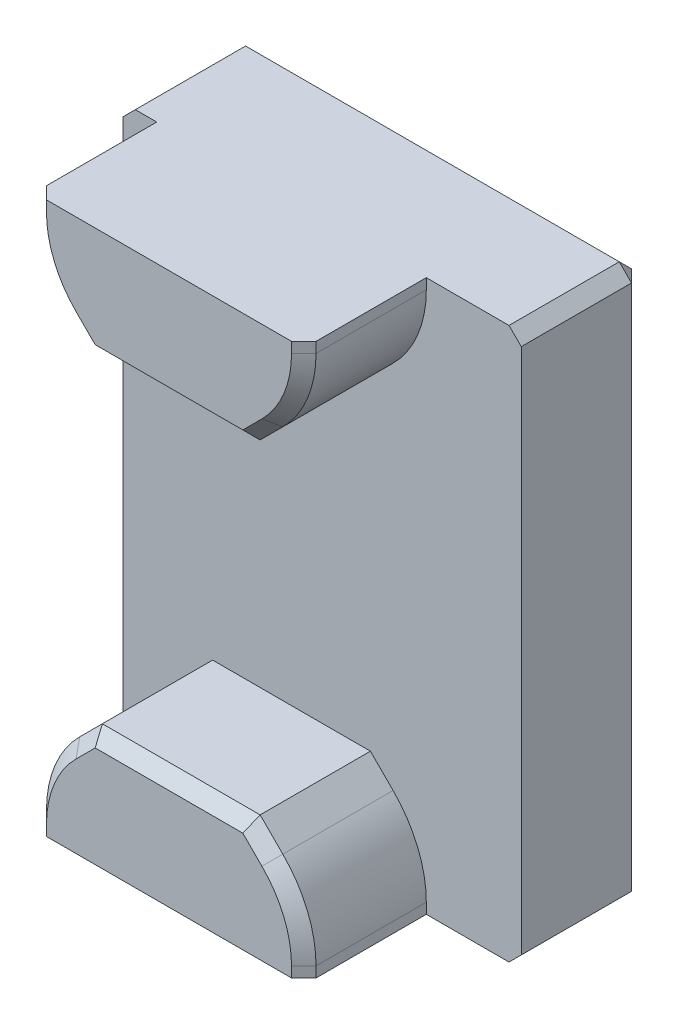
SolidWorks part; units mm, degrees
ref_plane "Front" through (0, 0, 0) normal (0, 0, 1) x (1, 0, 0)
ref_plane "Top" through (0, 0, 0) normal (0, 1, 0) x (1, 0, 0)
ref_plane "Right" through (0, 0, 0) normal (1, 0, 0) x (0, 0, -1)
sketch "Sketch1" plane through (0, 0, 0) normal (0, 0, 1) x (1, 0, 0)
  line L0 (2.75, -11.5) -> (2.75, -5) construction
  line L1 (-2.75, -4.5) -> (2.75, -4.5)
  line L2 (-2.75, -4.5) -> (-2.75, 4.5)
  line L3 (-2.75, 4.5) -> (2.75, 4.5)
  line L4 (2.75, -4.5) -> (2.75, 4.5) construction
  line L5 (-2.75, -4.5) -> (2.75, 4.5) construction
  line L6 (-2.75, 4.5) -> (2.75, -4.5) construction
  line L7 (2.35, -4.5) -> (3.75, -4.5) construction
  line L8 (2.75, 4.5) -> (3.75, 4.5)
  line L9 (3.75, 4.5) -> (3.75, -4.5)
  line L10 (3.75, -4.5) -> (2.75, -4.5)
  point P0 (0, 0)
extrude "Boss-Extrude1" add sketch "Sketch1" against normal blind 2
sketch "Sketch2" plane through (0, 0, 0) normal (0, 0, 1) x (1, 0, 0)
  line L9 (1.2879, -2.65) -> (-1.2879, -2.65)
  line L10 (-1.2879, -2.65) -> (-1.6581, -3.0203)
  line L11 (-2.2, -4.3284) -> (-2.2, -5.1716)
  line L12 (-1.6581, -6.4797) -> (-1.2879, -6.85)
  line L13 (-1.2879, -6.85) -> (1.2879, -6.85)
  line L14 (1.2879, -6.85) -> (1.6581, -6.4797)
  line L15 (2.2, -5.1716) -> (2.2, -4.3284)
  line L16 (1.6581, -3.0203) -> (1.2879, -2.65)
  line L41 (1.35, -7) -> (1.7642, -6.5858)
  line L46 (-1.35, -7) -> (1.35, -7)
  line L48 (-1.7642, -6.5858) -> (-1.35, -7)
  line L54 (-2.35, -4.3284) -> (-2.35, -5.1716)
  line L170 (-1.35, -2.5) -> (-1.7642, -2.9142)
  line L171 (1.35, -2.5) -> (-1.35, -2.5)
  line L172 (1.7642, -2.9142) -> (1.35, -2.5)
  line L173 (2.35, -5.1716) -> (2.35, -4.3284)
  line L174 (1.35, -7) -> (1.7642, -6.5858) construction
  line L175 (-1.35, -7) -> (1.35, -7) construction
  line L176 (-1.7642, -6.5858) -> (-1.35, -7) construction
  line L177 (-2.35, -4.3284) -> (-2.35, -5.1716) construction
  line L178 (-1.35, -2.5) -> (-1.7642, -2.9142) construction
  line L179 (1.35, -2.5) -> (-1.35, -2.5) construction
  line L180 (1.7642, -2.9142) -> (1.35, -2.5) construction
  line L181 (2.35, -5.1716) -> (2.35, -4.3284) construction
  line L182 (2.0738, -4.5) -> (-2.0738, -4.5)
  line L183 (-2.75, -4.5) -> (3.75, -4.5) construction
  line L184 (-2.0738, -4.5) -> (-2.2, -4.5)
  line L185 (2.0738, -4.5) -> (2.2, -4.5)
  line L186 (-2.75, -4.5) -> (3.75, -4.5) construction
  arc A7 (-1.6581, -3.0203) -> (-2.2, -4.3284) centre (-0.35, -4.3284) ccw
  circle A8 centre (0, -4.75) radius 2.25
  circle A10 centre (0, -4.75) radius 2.25 construction
  arc A11 (-2.2, -5.1716) -> (-1.6581, -6.4797) centre (-0.35, -5.1716) ccw
  arc A73 (1.6581, -6.4797) -> (2.2, -5.1716) centre (0.35, -5.1716) ccw
  arc A74 (2.2, -4.3284) -> (1.6581, -3.0203) centre (0.35, -4.3284) ccw
  arc A75 (-2.35, -5.1716) -> (-1.7642, -6.5858) centre (-0.35, -5.1716) ccw
  arc A76 (-1.7642, -2.9142) -> (-2.35, -4.3284) centre (-0.35, -4.3284) ccw
  arc A77 (2.35, -4.3284) -> (1.7642, -2.9142) centre (0.35, -4.3284) ccw
  arc A78 (1.7642, -6.5858) -> (2.35, -5.1716) centre (0.35, -5.1716) ccw
  arc A79 (-2.35, -5.1716) -> (-1.7642, -6.5858) centre (-0.35, -5.1716) ccw construction
  arc A80 (-1.7642, -2.9142) -> (-2.35, -4.3284) centre (-0.35, -4.3284) ccw construction
  arc A81 (2.35, -4.3284) -> (1.7642, -2.9142) centre (0.35, -4.3284) ccw construction
  arc A82 (1.7642, -6.5858) -> (2.35, -5.1716) centre (0.35, -5.1716) ccw construction
  dimension "D1" = 0
  dimension "D2" = 0
  dimension "D3" = 0.15
extrude "Slot Tab" add sketch "Sketch2" along normal blind 2 contours L15 A74 L16 L9 L10 A7 L11 L184 L182 L185 region at (1.6006, -3.1532, 0) region at (0, -3.6837, 0) region at (-1.6006, -3.1532, 0)
mirror "Slot Tabs" about plane through (0, 0, 0) normal (0, 1, 0) of "Slot Tab"
chamfer "Deburs" distance 0.2 angle 45 22 edges at (0.5, -4.5, -2) (-2.75, -4.5, -1) (-2.75, 0, -2) (-2.75, 4.5, -1) (0.5, 4.5, -2) (3.75, 0, -2) (3.75, -4.5, -1) (3.75, 4.5, -1) (2.2, -4.4142, 2) (-2.2, -4.4142, 2) (2.0592, -3.6205, 2) (-2.0592, -3.6205, 2) (1.473, -2.8351, 2) (0, -2.65, 2) (-1.473, -2.8351, 2) (2.2, 4.4142, 2) (-2.2, 4.4142, 2) (2.0592, 3.6205, 2) (-2.0592, 3.6205, 2) (1.473, 2.8351, 2) (0, 2.65, 2) (-1.473, 2.8351, 2)
sketch "Sketch3" [suppressed] plane through (0, 0, -2) normal (0, 0, -1) x (-1, 0, 0)
  line L4 (2.75, 4.5) -> (-3.75, 4.5)
  line L6 (2.75, 4.5) -> (-3.75, 4.5)
  line L12 (2.75, -4.5) -> (2.75, 4.5)
  line L14 (2.75, -4.5) -> (2.75, 4.5)
  line L16 (-3.75, -4.5) -> (2.75, -4.5)
  line L17 (-3.75, -4.5) -> (2.75, -4.5)
  line L18 (-3.75, 4.5) -> (-3.75, -4.5)
  line L19 (-3.75, 4.5) -> (-3.75, -4.5)
  dimension "D1" = 0
extrude "Stopper Clearance" [suppressed] add sketch "Sketch3" along normal blind 2
sketch "Sketch4" [suppressed] plane through (0, 0, -4) normal (0, 0, -1) x (-1, 0, 0)
  line L1 (2.875, -11) -> (-6.875, -11)
  line L2 (2.875, -11) -> (2.875, 11)
  line L3 (2.875, 11) -> (-6.875, 11)
  line L4 (-6.875, -11) -> (-6.875, 11)
  line L5 (2.875, -11) -> (-6.875, 11) construction
  line L6 (2.875, 11) -> (-6.875, -11) construction
  point P0 (-2, 0)
  dimension "D1" = 2
  dimension "D2" = 22
  dimension "D3" = 9.75
extrude "Stopper" [suppressed] add sketch "Sketch4" along normal blind 2.5
chamfer "Deburs 2" [suppressed] distance 0.2 angle 45
chamfer "Chamfer3" [suppressed] distance 1 angle 45
